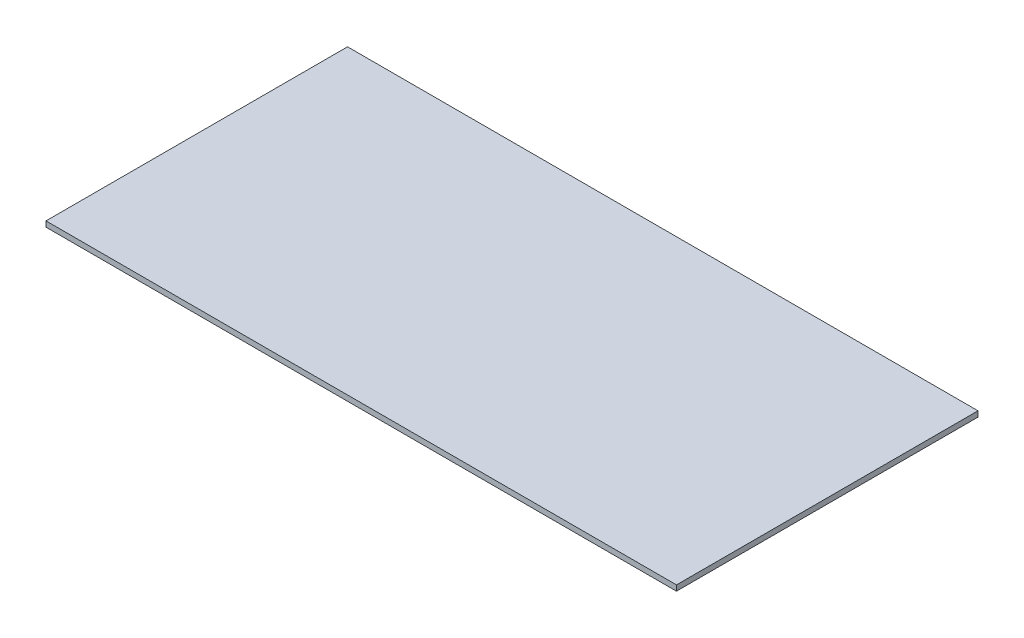
SolidWorks part; units mm, degrees
material "PC High Viscosity"
ref_plane "Front Plane" through (0, 0, 0) normal (0, 0, 1) x (1, 0, 0)
ref_plane "Top Plane" through (0, 0, 0) normal (0, 1, 0) x (1, 0, 0)
ref_plane "Right Plane" through (0, 0, 0) normal (1, 0, 0) x (0, 0, -1)
sketch "Sketch1" plane through (0, 0, 0) normal (0, 1, 0) x (1, 0, 0)
  line L1 (0, 0) -> (584.2, 0)
  line L2 (0, 0) -> (0, 279.4)
  line L3 (0, 279.4) -> (584.2, 279.4)
  line L4 (584.2, 0) -> (584.2, 279.4)
  dimension "D1" = 584.2
  dimension "D2" = 279.4
extrude "Boss-Extrude1" add sketch "Sketch1" along normal blind 5.08
